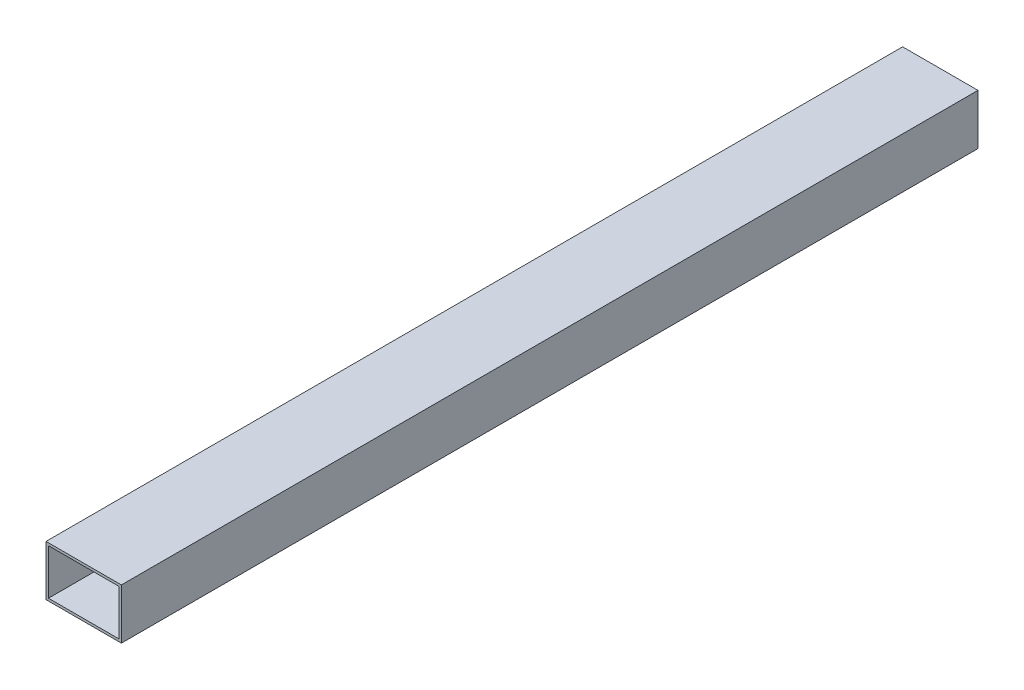
SolidWorks part; units mm, degrees
ref_plane "Alzado" through (0, 0, 0) normal (0, 0, 1) x (1, 0, 0)
ref_plane "Planta" through (0, 0, 0) normal (0, 1, 0) x (1, 0, 0)
ref_plane "Vista lateral" through (0, 0, 0) normal (1, 0, 0) x (0, 0, -1)
sketch "Croquis2" plane through (0, 0, 0) normal (0, 0, 1) x (1, 0, 0)
  line L1 (38.1, -25.5) -> (-38.1, -25.5)
  line L2 (38.1, -25.5) -> (38.1, 25.5)
  line L3 (38.1, 25.5) -> (-38.1, 25.5)
  line L4 (-38.1, -25.5) -> (-38.1, 25.5)
  line L5 (38.1, -25.5) -> (-38.1, 25.5) construction
  line L6 (38.1, 25.5) -> (-38.1, -25.5) construction
  point P0 (0, 0)
  point P6 (0, 25.5)
  dimension "D1" = 51
  dimension "D2" = 76.2
extrude "Saliente-Extruir1" add sketch "Croquis2" along normal mid plane 866
sketch "Croquis6" plane through (0, 0, 433) normal (0, 0, 1) x (1, 0, 0)
  line L4 (-38.1, 25.5) -> (-38.1, -25.5)
  line L5 (-38.1, -25.5) -> (38.1, -25.5)
  line L6 (38.1, -25.5) -> (38.1, 25.5)
  line L7 (38.1, 25.5) -> (-38.1, 25.5)
  line L8 (-38.1, 25.5) -> (-38.1, -25.5)
  line L9 (-38.1, -25.5) -> (38.1, -25.5)
  line L10 (38.1, -25.5) -> (38.1, 25.5)
  line L11 (38.1, 25.5) -> (-38.1, 25.5)
  line L16 (-35.6, 23) -> (-35.6, -23)
  line L17 (-35.6, -23) -> (35.6, -23)
  line L18 (35.6, -23) -> (35.6, 23)
  line L19 (35.6, 23) -> (-35.6, 23)
  line L20 (-35.6, 23) -> (-35.6, -23)
  line L21 (-35.6, -23) -> (35.6, -23)
  line L22 (35.6, -23) -> (35.6, 23)
  line L23 (35.6, 23) -> (-35.6, 23)
  dimension "D1" = 0
  dimension "D2" = 2.5
extrude "Cortar-Extruir1" cut sketch "Croquis6" against normal blind 900 contours L22 L23 L20 L21 region at (0, 0, 433)
